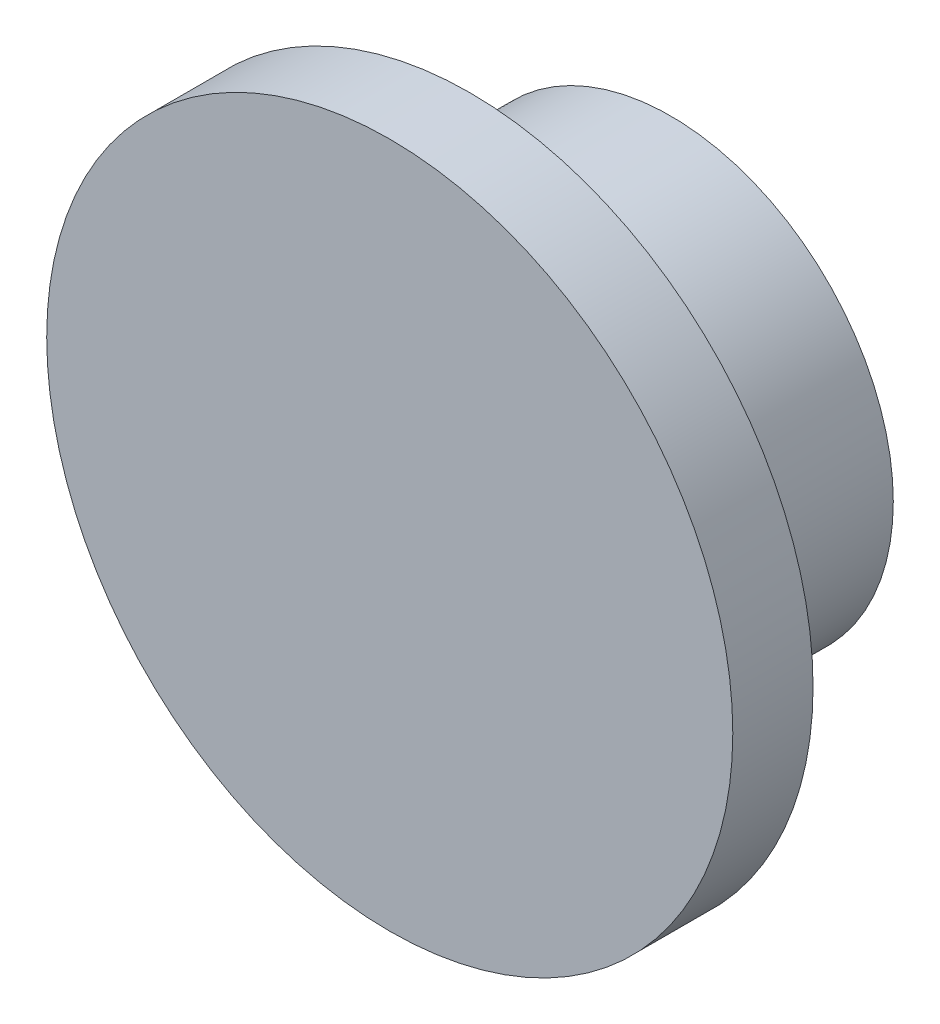
SolidWorks part; units mm, degrees
ref_plane "Front Plane" through (0, 0, 0) normal (0, 0, 1) x (1, 0, 0)
ref_plane "Top Plane" through (0, 0, 0) normal (0, 1, 0) x (1, 0, 0)
ref_plane "Right Plane" through (0, 0, 0) normal (1, 0, 0) x (0, 0, -1)
sketch "Sketch1" plane through (0, 0, 0) normal (0, 0, 1) x (1, 0, 0)
  circle A0 centre (0, 0) radius 2.55
  circle A3 centre (0, 0) radius 2.35 construction
  circle A4 centre (0, 0) radius 5.55
  dimension "D1" = 4.7
  dimension "D2" = 0.2
  dimension "D3" = 3
extrude "Boss-Extrude1" add sketch "Sketch1" against normal blind 5
sketch "Sketch2" plane through (0, 0, 0) normal (0, 0, 1) x (1, 0, 0)
  circle A2 centre (0, 0) radius 8.55
  circle A3 centre (0, 0) radius 8.55
  dimension "D1" = 3
extrude "Boss-Extrude2" add sketch "Sketch2" along normal blind 2
thread "Thread1" pitch 0.8 method extrude profile "Thread Profile1" start angle 0, offset 0, length 4.5, pitch 0.8, diameter 5.1
ref_plane "Plane1" through (2.55, 0, -5) normal (0, -1, 0) x (1, 0, 0)
sketch "Thread Profile1" plane through (2.55, 0, -5) normal (0, -1, 0) x (1, 0, 0)
  line L0 (0, 0) -> (0, 0.8) construction
  line L11 (0, 0) -> (0, 0.7)
  line L12 (0, 0.7) -> (-0.433, 0.45)
  line L13 (-0.433, 0.45) -> (-0.433, 0.25)
  line L15 (-0.433, 0.25) -> (0, 0)
  line L17 (-0.433, 0.35) -> (0, 0.35) construction
  point P2 (0, 0)
  dimension "Pitch" = 0.8
  dimension "Profile_Angle" = 60
  dimension "Profile_Land" = 0.2
  dimension "Profile_Height" = 0.433
sketch "Sketch3" [suppressed] plane through (0, 0, 2) normal (0, 0, 1) x (1, 0, 0)
  line L0 (0, 4.3) -> (0, -4.3) construction
  line L1 (-0.375, -4.3) -> (0.375, -4.3)
  line L2 (-0.375, 4.3) -> (0.375, 4.3)
  line L3 (0.375, -4.3) -> (0.375, 4.3)
  line L4 (-0.375, 4.3) -> (-0.375, -4.3)
  circle A0 centre (0, 0) radius 4.3 construction
  point P7 (0, 0)
  point P11 (0, -4.3)
  point P14 (0, 4.3)
  dimension "D1" = 0.75
extrude "Cut-Extrude1" [suppressed] cut sketch "Sketch3" against normal blind 1
equation "\"ThreadWalls\" = 3"
equation "\"D3@Sketch1\"=\"ThreadWalls\""
equation "\"BaseFlange\" = 3"
equation "\"D1@Sketch2\"=\"BaseFlange\""
